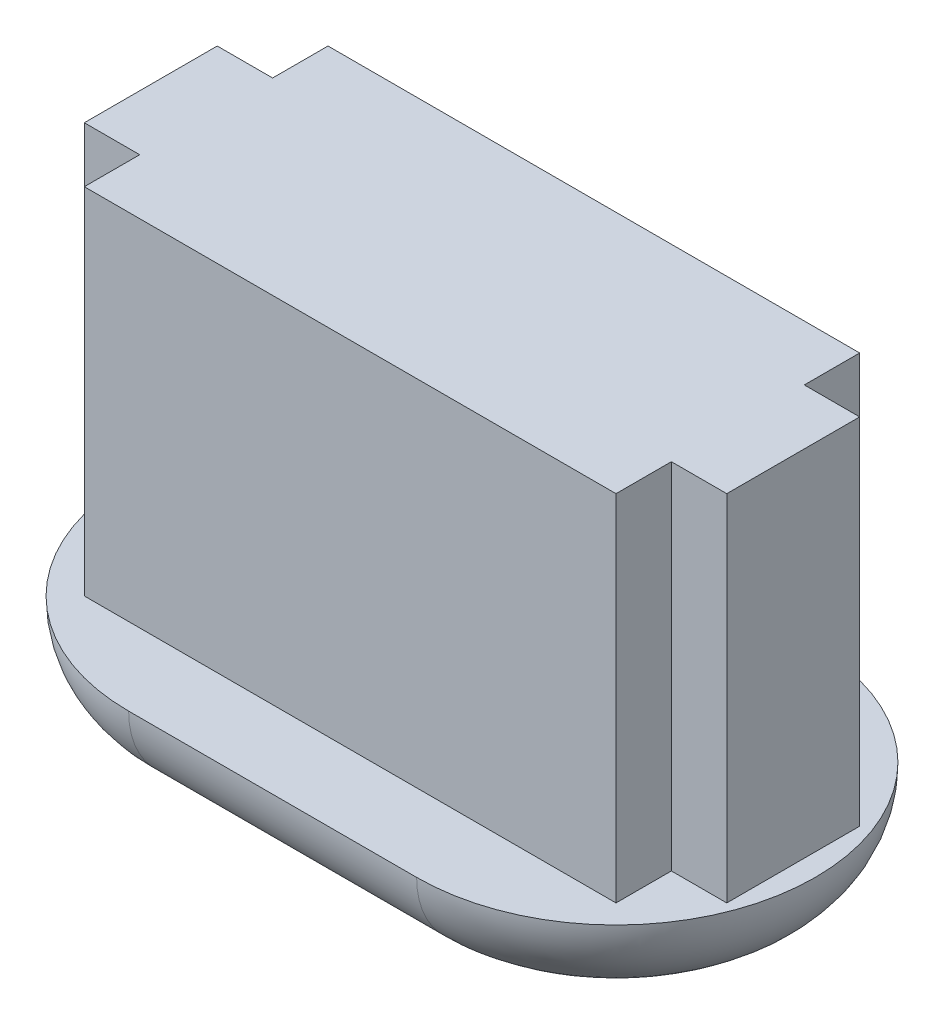
SolidWorks part; units mm, degrees
ref_plane "Plan de face" through (0, 0, 0) normal (0, 0, 1) x (1, 0, 0)
ref_plane "Plan de dessus" through (0, 0, 0) normal (0, 1, 0) x (1, 0, 0)
ref_plane "Plan de droite" through (0, 0, 0) normal (1, 0, 0) x (0, 0, -1)
sketch "Esquisse1" plane through (0, 0, 0) normal (0, 1, 0) x (1, 0, 0)
  line L0 (0, 0) -> (6.5, 0) construction
  line L1 (0, 4.5) -> (6.5, 4.5)
  line L2 (0, -4.5) -> (6.5, -4.5)
  arc A0 (0, 4.5) -> (0, -4.5) centre (0, 0) ccw
  arc A1 (6.5, -4.5) -> (6.5, 4.5) centre (6.5, 0) ccw
  point P1 (3.25, 0)
  point P13 (-4.5, 0)
  point P14 (11, 0)
  dimension "D1" = 15.5
  dimension "D3" = 9
extrude "Boss.-Extru.1" add sketch "Esquisse1" along normal blind 2
fillet "Congé1" radius 2 4 edges at (3.25, 0, -4.5) (11, 0, 0) (-4.5, 0, 0) (3.25, 0, 4.5)
sketch "Esquisse2" plane through (0, 2, 0) normal (0, 1, 0) x (1, 0, 0)
  line L0 (6.5, 4.5) -> (0, 4.5) construction
  line L1 (-2.75, -2.75) -> (9.25, -2.75)
  line L2 (-2.75, -2.75) -> (-2.75, 2.75)
  line L3 (-2.75, 2.75) -> (9.25, 2.75)
  line L4 (9.25, -2.75) -> (9.25, 2.75)
  line L5 (3.25, -4.5) -> (3.25, 4.5) construction
  line L6 (-4, -1.5) -> (-2.75, -1.5)
  line L7 (-4, -1.5) -> (-4, 1.5)
  line L8 (-4, 1.5) -> (-2.75, 1.5)
  line L9 (-2.75, -1.5) -> (-2.75, 1.5)
  line L10 (0, -4.5) -> (6.5, -4.5) construction
  line L11 (10.5, 1.5) -> (9.25, 1.5)
  line L12 (10.5, -1.5) -> (9.25, -1.5)
  line L13 (10.5, -1.5) -> (10.5, 1.5)
  point P4 (3.25, 4.5)
  point P8 (-2.75, 0)
  point P12 (3.25, 2.75)
  point P17 (-2.75, 0)
  point P18 (3.25, 0)
  arc M3 (0, 4.5) -> (0, -4.5) centre (0, 0) ccw
  arc M5 (6.5, -4.5) -> (6.5, 4.5) centre (6.5, 0) ccw
  dimension "D1" = 12
  dimension "D2" = 5.5
  dimension "D3" = 3
  dimension "D4" = 1.25
extrude "Boss.-Extru.2" add sketch "Esquisse2" along normal blind 8 contours L5 L1 L4 L3 | L1 L5 L3 L2 | L8 L6 L2 M3 | L12 L11 L4 M5 region at (0.25, 2, 0) region at (6.25, 2, 0) region at (-3.375, 2, 0) region at (9.875, 2, 0)
sketch "Esquisse4" plane through (0, 0, 0) normal (0, -1, 0) x (1, 0, 0)
  line L6 (6.5, 1.5) -> (0, 1.5)
  line L7 (0, -1.5) -> (6.5, -1.5)
  line L8 (6.5, 1.5) -> (0, 1.5)
  line L9 (0, -1.5) -> (6.5, -1.5)
  arc A8 (6.5, -1.5) -> (6.5, 1.5) centre (6.5, 0) ccw
  arc A9 (0, 1.5) -> (0, -1.5) centre (0, 0) ccw
  arc A10 (6.5, -1.5) -> (6.5, 1.5) centre (6.5, 0) ccw
  arc A11 (0, 1.5) -> (0, -1.5) centre (0, 0) ccw
  dimension "D1" = 1
extrude "Enlèv. mat.-Extru.1" cut sketch "Esquisse4" against normal blind 5
